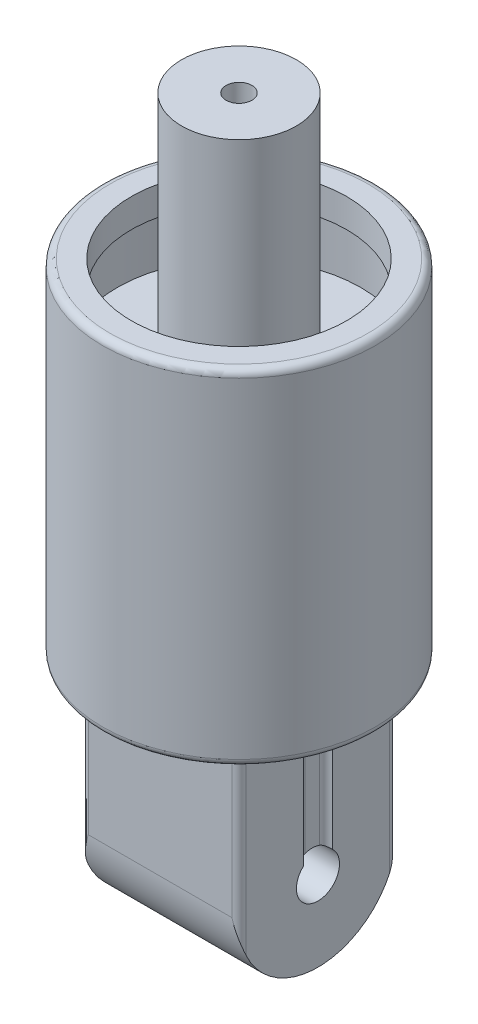
SolidWorks part; units mm, degrees
ref_plane "Plan de face" through (0, 0, 0) normal (0, 0, 1) x (1, 0, 0)
ref_plane "Plan de dessus" through (0, 0, 0) normal (0, 1, 0) x (1, 0, 0)
ref_plane "Plan de droite" through (0, 0, 0) normal (1, 0, 0) x (0, 0, -1)
sketch "Esquisse1" plane through (0, 0, 0) normal (0, 0, 1) x (1, 0, 0)
  line L0 (0, 0) -> (0, 12) construction
  line L1 (0, 0) -> (4.75, 0) construction
  line L2 (4.75, 0) -> (4.75, 12) construction
  line L3 (4.75, 12) -> (0, 12) construction
  line L4 (1, 12) -> (1, 0) construction
  line L5 (2, 9) -> (2, 17)
  line L6 (4.5, 12) -> (3.75, 12)
  line L7 (4.75, 11.75) -> (4.75, 0.25)
  line L8 (4.5, 0) -> (1, 0)
  line L9 (3.75, 12) -> (3.75, 11)
  line L10 (3.75, 11) -> (4.25, 11)
  line L11 (4.25, 11) -> (4.25, 9)
  line L12 (4.25, 9) -> (2, 9)
  line L13 (2, 9) -> (2, 12) construction
  line L14 (2, 17) -> (0.45, 17)
  line L15 (0.45, 17) -> (0.45, 12)
  line L16 (0.45, 12) -> (1, 12)
  line L17 (1, 12) -> (1, 0)
  arc A0 (4.75, 0.25) -> (4.5, 0) centre (4.5, 0.25) cw
  arc A1 (4.75, 11.75) -> (4.5, 12) centre (4.5, 11.75) ccw
  dimension "D9" = 0.25
  dimension "D1" = 12
  dimension "D2" = 9.5
  dimension "D3" = 2
  dimension "D4" = 1
  dimension "D5" = 1
  dimension "D6" = 0.5
  dimension "D7" = 2
  dimension "D8" = 1
  dimension "D10" = 5
  dimension "D11" = 0.9
revolve "Révolution1" add sketch "Esquisse1" angle 360 about L0
sketch "Esquisse4" plane through (0, 0, 0) normal (0, -1, 0) x (1, 0, 0)
  line L1 (-2.5, -2.75) -> (2.5, -2.75)
  line L2 (-2.75, -2.5) -> (-2.75, 2.5)
  line L3 (-2.5, 2.75) -> (2.5, 2.75)
  line L4 (2.75, -2.5) -> (2.75, 2.5)
  line L5 (-2.75, -2.75) -> (2.75, 2.75) construction
  line L6 (-2.75, 2.75) -> (2.75, -2.75) construction
  circle A0 centre (0, 0) radius 1 construction
  circle A1 centre (0, 0) radius 1
  arc A2 (-2.5, -2.75) -> (-2.75, -2.5) centre (-2.5, -2.5) cw
  arc A3 (2.75, -2.5) -> (2.5, -2.75) centre (2.5, -2.5) cw
  arc A4 (2.75, 2.5) -> (2.5, 2.75) centre (2.5, 2.5) ccw
  arc A5 (-2.75, 2.5) -> (-2.5, 2.75) centre (-2.5, 2.5) cw
  point P0 (0, 0)
  dimension "D2" = 0.25
  dimension "D1" = 5.5
extrude "Boss.-Extru.2" add sketch "Esquisse4" along normal blind 8
sketch "Esquisse5" plane through (2.75, 0, 0) normal (1, 0, 0) x (0, 0, -1)
  line L0 (-2.75, -8) -> (-2.75, 0) construction
  line L1 (2.75, -8) -> (2.75, 0) construction
  line L2 (2.75, -5.25) -> (-2.75, -5.25) construction
  line L3 (2.5, -8) -> (-2.5, -8) construction
  line L4 (2.75, -5.25) -> (2.75, -8)
  line L5 (2.75, -8) -> (-2.75, -8)
  line L6 (-2.75, -8) -> (-2.75, -5.25)
  arc A0 (-2.75, -5.25) -> (2.75, -5.25) centre (0, -5.25) ccw
  circle A1 centre (0, -5.25) radius 0.75
  line M2 (-2.5, 0) -> (-2.5, -8)
  line M3 (-2.5, -8) -> (2.5, -8)
  line M4 (2.5, -8) -> (2.5, 0)
  dimension "D1" = 1.5
extrude "Enlèv. mat.-Extru.1" cut sketch "Esquisse5" against normal through all contours A0 M2 M3 | A0 L5 M4 | A0 L6 L5 M2 | A0 L5 L4 M4 | L2 A1 | A1 L2 region at (2.75, -6.9922, -2.6346) region at (2.75, -7.5583, -1.917) region at (2.75, -5.5683, 0) region at (2.75, -4.9317, 0) region at (2.75, -7.5583, 1.917) region at (2.75, -6.9922, 2.6346)
sketch "Esquisse6" plane through (0, 0, -2.75) normal (0, 0, 1) x (1, 0, 0)
  line L0 (-1, -8) -> (-1, -2.5)
  line L1 (-1, -2.5) -> (1, -2.5)
  line L2 (1, -2.5) -> (1, -8)
  line L3 (1, -8) -> (-1, -8)
  dimension "D1" = 2
  dimension "D2" = 2.5
extrude "Enlèv. mat.-Extru.2" cut sketch "Esquisse6" along normal up to next
fillet "Congé1" radius 0.25 6 edges at (-1, -3.875, -2.75) (-1, -7.1945, -1.9445) (-0.0866, -7.8132, 0.9962) (1, -7.1945, -1.9445) (1, -3.875, -2.75) (0, -2.5, -2.75)
sketch "Esquisse7" plane through (-2.75, 0, 0) normal (-1, 0, 0) x (0, 0, 1)
  line L0 (0, 0) -> (0, -4.5) construction
  line L1 (2.5, 0) -> (-2.5, 0) construction
  line L2 (-0.5, -4.691) -> (0.5, -4.691)
  line L3 (-0.5, -4.691) -> (-0.5, 0)
  line L4 (-0.5, 0) -> (0.5, 0)
  line L5 (0.5, -4.691) -> (0.5, 0)
  line L6 (-0.5, -4.691) -> (0.5, 0) construction
  line L7 (-0.5, 0) -> (0.5, -4.691) construction
  circle A0 centre (0, -5.25) radius 0.75 construction
  point P6 (0, -2.3455)
  dimension "D1" = 1
extrude "Enlèv. mat.-Extru.3" cut sketch "Esquisse7" against normal blind 0.2
fillet "Congé2" radius 0.25 2 edges at (-2.55, -2.3455, 0.5) (-2.55, -2.3455, -0.5)
mirror "Symétrie1" about plane through (0, 0, 0) normal (1, 0, 0) of "Enlèv. mat.-Extru.3", "Congé2"
